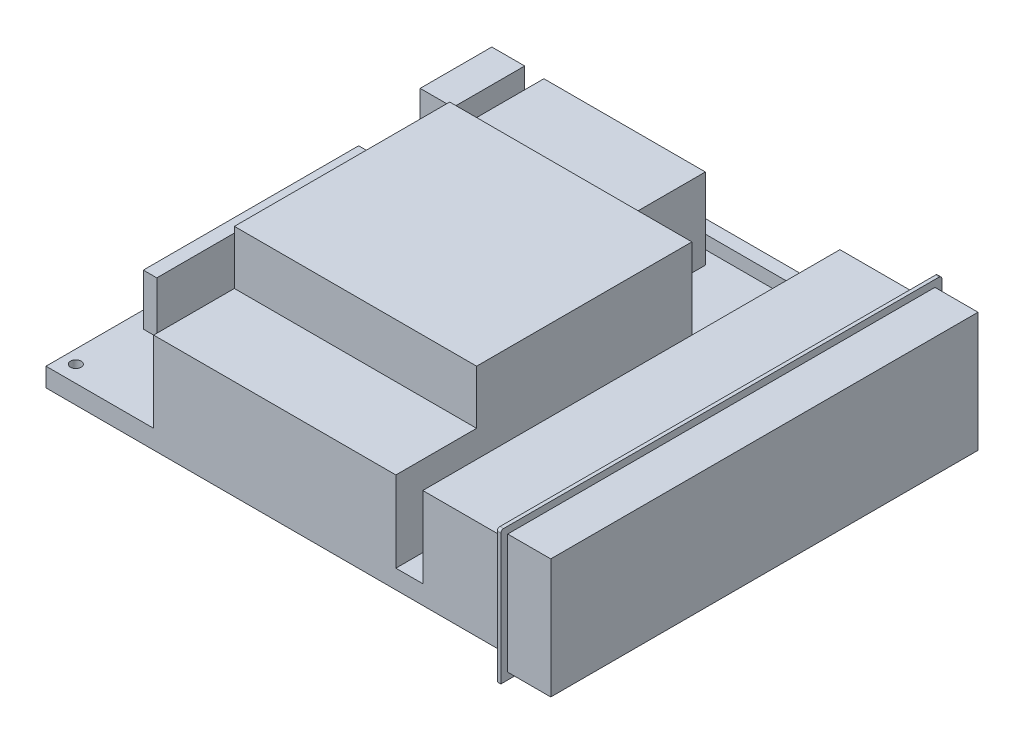
SolidWorks part; units mm, degrees
ref_plane "Front Plane" through (0, 0, 0) normal (0, 0, 1) x (1, 0, 0)
ref_plane "Top Plane" through (0, 0, 0) normal (0, 1, 0) x (1, 0, 0)
ref_plane "Right Plane" through (0, 0, 0) normal (1, 0, 0) x (0, 0, -1)
sketch "Sketch1" plane through (0, 0, 0) normal (0, 1, 0) x (1, 0, 0)
  line L1 (-85, -85) -> (85, -85)
  line L2 (-85, -85) -> (-85, 85)
  line L3 (-85, 85) -> (85, 85)
  line L4 (85, -85) -> (85, 85)
  line L5 (-85, -85) -> (85, 85) construction
  line L6 (-85, 85) -> (85, -85) construction
  point P0 (0, 0)
  dimension "D1" = 170
extrude "alusplaat" add sketch "Sketch1" along normal blind 2
sketch "Sketch2" plane through (0, 2, 0) normal (0, 1, 0) x (-1, 0, 0)
  line L1 (-85, 85) -> (-55, 85)
  line L2 (-85, 85) -> (-85, -70)
  line L3 (-85, -70) -> (-55, -70)
  line L4 (-55, 85) -> (-55, -70)
  dimension "D1" = 155
  dimension "D2" = 30
extrude "pistikud" add sketch "Sketch2" along normal blind 35
sketch "Sketch3" plane through (0, 2, 0) normal (0, 1, 0) x (1, 0, 0)
  line L0 (-85, -85) -> (55, -85) construction
  line L1 (-45, -85) -> (45, -85)
  line L2 (-45, -85) -> (-45, 25)
  line L3 (-45, 25) -> (45, 25)
  line L4 (45, -85) -> (45, 25)
  line L5 (-85, 85) -> (-85, -85) construction
  dimension "D1" = 90
  dimension "D2" = 40
  dimension "D3" = 110
extrude "cpu+mälud" add sketch "Sketch3" along normal blind 55
sketch "Sketch4" plane through (0, 2, 0) normal (0, 1, 0) x (1, 0, 0)
  line L1 (5, 35) -> (-55, 35)
  line L2 (5, 35) -> (5, 70)
  line L3 (5, 70) -> (-55, 70)
  line L4 (-55, 35) -> (-55, 70)
  line L5 (-85, 85) -> (-85, -85) construction
  line L6 (85, 85) -> (-85, 85) construction
  dimension "D1" = 35
  dimension "D2" = 60
  dimension "D3" = 30
  dimension "D4" = 15
extrude "sinine radikas" add sketch "Sketch4" along normal blind 35
sketch "Sketch5" plane through (0, 2, 0) normal (0, 1, 0) x (-1, 0, 0)
  line L0 (85, -85) -> (85, 85) construction
  line L1 (45, -75) -> (-45, -75)
  line L2 (45, -75) -> (45, -80)
  line L3 (45, -80) -> (-45, -80)
  line L4 (-45, -75) -> (-45, -80)
  line L5 (-85, -85) -> (85, -85) construction
  dimension "D1" = 90
  dimension "D2" = 40
  dimension "D3" = 5
  dimension "D4" = 5
extrude "pcie pesa" add sketch "Sketch5" along normal blind 10
sketch "Sketch6" plane through (0, 2, 0) normal (0, 1, 0) x (-1, 0, 0)
  line L1 (67.672, -48.9124) -> (79.8888, -48.9124)
  line L2 (67.672, -48.9124) -> (67.672, -75.5395)
  line L3 (67.672, -75.5395) -> (79.8888, -75.5395)
  line L4 (79.8888, -48.9124) -> (79.8888, -75.5395)
extrude "raid pesad" add sketch "Sketch6" along normal blind 30
sketch "Sketch7" plane through (0, 2, 0) normal (0, 1, 0) x (-1, 0, 0)
  line L1 (85, -85) -> (-85, -85)
  line L2 (85, -85) -> (85, 85)
  line L3 (85, 85) -> (-85, 85)
  line L4 (-85, -85) -> (-85, 85)
extrude "üleüldine müra" add sketch "Sketch7" along normal blind 5
sketch "Sketch8" plane through (0, 7, 0) normal (0, 1, 0) x (-1, 0, 0)
  line L0 (-85, -85) -> (85, -85) construction
  line L1 (78.8401, -25) -> (73.8401, -25)
  line L2 (78.8401, -25) -> (78.8401, 55)
  line L3 (78.8401, 55) -> (73.8401, 55)
  line L4 (73.8401, -25) -> (73.8401, 55)
  dimension "D1" = 5
  dimension "D2" = 80
  dimension "D3" = 60
extrude "patrei ja igasugused lülitid" add sketch "Sketch8" along normal blind 19
sketch "Sketch9" plane through (0, 57, 0) normal (0, 1, 0) x (-1, 0, 0)
  line L0 (-45, 85) -> (-45, -25) construction
  line L1 (45, -25) -> (-45, -25)
  line L2 (45, -25) -> (45, 55)
  line L3 (45, 55) -> (-45, 55)
  line L4 (-45, -25) -> (-45, 55)
  dimension "D1" = 80
extrude "mälud" cut sketch "Sketch9" against normal blind 20 flip side to cut
sketch "Sketch10" plane through (0, 7, 0) normal (0, 1, 0) x (1, 0, 0)
  line L0 (85, 85) -> (-85, 85) construction
  line L1 (74.84, 78.65) -> (-80.1, 78.65) construction
  line L2 (74.84, 78.65) -> (74.84, -78.83) construction
  line L3 (74.84, -78.83) -> (-80.1, -78.83) construction
  line L4 (-80.1, 78.65) -> (-80.1, -78.83) construction
  line L5 (85, 70) -> (85, 85) construction
  circle A0 centre (74.84, 78.65) radius 1.98
  circle A1 centre (-80.1, 78.65) radius 1.98
  circle A2 centre (-80.1, -78.83) radius 1.98
  circle A3 centre (51.98, -78.83) radius 1.98
  dimension "D6" = 3.96
  dimension "D1" = 6.35
  dimension "D2" = 10.16
  dimension "D3" = 154.94
  dimension "D4" = 157.48
  dimension "D5" = 22.86
extrude "Cut-Extrude2" cut sketch "Sketch10" against normal up to next
sketch "Sketch13" plane through (0, 7, 0) normal (0, 1, 0) x (1, 0, 0)
  line L1 (74.84, 78.65) -> (87.11, 78.65)
  line L2 (74.84, 78.65) -> (74.84, -92.9265)
  line L3 (74.84, -92.9265) -> (87.11, -92.9265)
  line L4 (87.11, 78.65) -> (87.11, -92.9265)
  dimension "D1" = 12.27
ref_plane "Plane2" through (87.11, 0, 0) normal (1, 0, 0) x (0, 0, -1)
sketch "Sketch11" plane through (87.11, 0, 0) normal (1, 0, 0) x (0, 0, -1)
  line L0 (-85, 0) -> (85, 0) construction
  line L1 (-86.875, -3.81) -> (71.875, -3.81) construction
  line L2 (-86.875, -3.81) -> (-86.875, 40.64) construction
  line L3 (-86.875, 40.64) -> (71.875, 40.64) construction
  line L4 (71.875, -3.81) -> (71.875, 40.64) construction
  line L5 (-88.415, 43.18) -> (73.415, 43.18)
  line L6 (71.875, 18.415) -> (70, 18.415) construction
  line L7 (70, 37) -> (70, 7) construction
  line L8 (-86.875, 18.415) -> (-85, 18.415) construction
  line L9 (-85, 37) -> (-85, 0) construction
  line L10 (74.415, -5.35) -> (74.415, 42.18)
  line L11 (-89.415, -6.35) -> (73.415, -6.35)
  line L12 (-89.415, -6.35) -> (-89.415, 42.18)
  line L13 (-89.415, -6.35) -> (74.415, -6.35) construction
  line L14 (74.415, -6.35) -> (74.415, 43.18) construction
  line L15 (-89.415, 43.18) -> (74.415, 43.18) construction
  line L16 (-89.415, -6.35) -> (-89.415, 43.18) construction
  arc A0 (73.415, -6.35) -> (74.415, -5.35) centre (73.415, -5.35) ccw
  arc A1 (74.415, 42.18) -> (73.415, 43.18) centre (73.415, 42.18) ccw
  arc A2 (-88.415, 43.18) -> (-89.415, 42.18) centre (-88.415, 42.18) ccw
  dimension "D5" = 1
  dimension "D1" = 158.75
  dimension "D2" = 44.45
  dimension "D3" = 3.81
  dimension "D4" = 2.54
extrude "Boss-Extrude1" add sketch "Sketch11" along normal blind 1.32
sketch "Sketch12" plane through (88.43, 0, 0) normal (1, 0, 0) x (0, 0, -1)
  line L1 (-86.875, -3.81) -> (71.875, -3.81)
  line L2 (-86.875, -3.81) -> (-86.875, 40.64)
  line L3 (-86.875, 40.64) -> (71.875, 40.64)
  line L4 (71.875, -3.81) -> (71.875, 40.64)
  line L5 (-88.415, 43.18) -> (73.415, 43.18)
  line L10 (74.415, -5.35) -> (74.415, 42.18)
  line L11 (-89.415, -6.35) -> (73.415, -6.35)
  line L12 (-89.415, -6.35) -> (-89.415, 42.18)
  line L13 (-89.415, -6.35) -> (74.415, -6.35) construction
  line L14 (74.415, -6.35) -> (74.415, 43.18) construction
  line L15 (-89.415, 43.18) -> (74.415, 43.18) construction
  line L16 (-89.415, -6.35) -> (-89.415, 43.18) construction
  arc A0 (73.415, -6.35) -> (74.415, -5.35) centre (73.415, -5.35) ccw
  arc A1 (74.415, 42.18) -> (73.415, 43.18) centre (73.415, 42.18) ccw
  arc A2 (-88.415, 43.18) -> (-89.415, 42.18) centre (-88.415, 42.18) ccw
  arc A5 (-88.415, 43.18) -> (-89.415, 42.18) centre (-88.415, 42.18) ccw construction
  dimension "D5" = 1
  dimension "D1" = 158.75
  dimension "D2" = 44.45
  dimension "D4" = 2.54
extrude "Boss-Extrude2" add sketch "Sketch12" along normal blind 16 contours L1 L4 L3 L2 region at (88.43, 18.415, 7.5)
